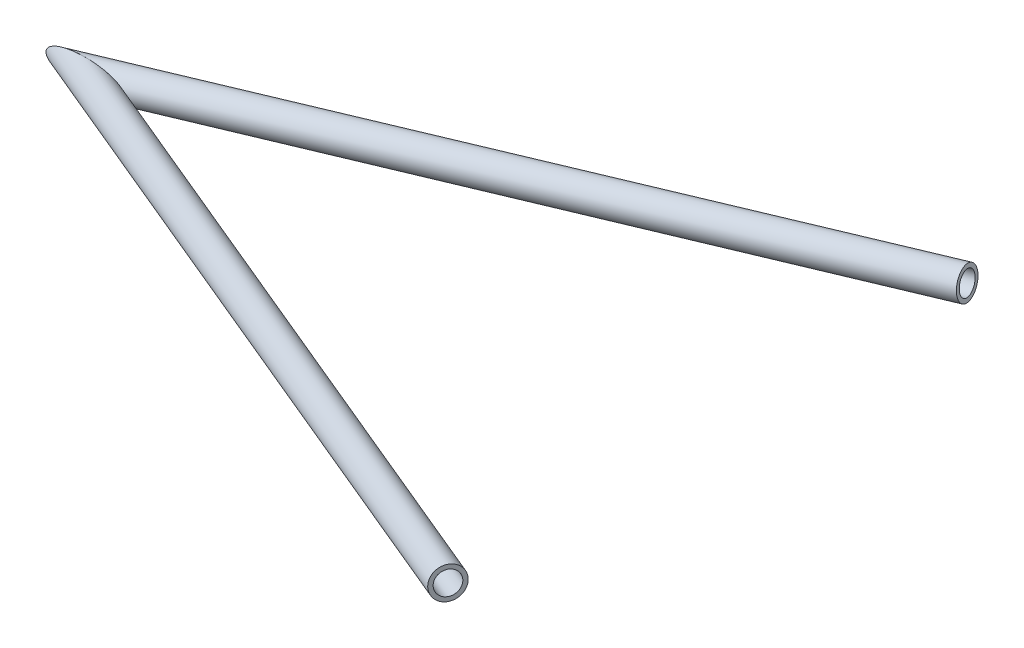
SolidWorks part; units mm, degrees
note: '?' marks a value the reader was unsure of.
material "AISI 4130 Steel, annealed at 865C"
ref_plane "Front Plane" through (0, 0, 0) normal (0, 0, 1) x (1, 0, 0)
ref_plane "Top Plane" through (0, 0, 0) normal (0, 1, 0) x (1, 0, 0)
ref_plane "Right Plane" through (0, 0, 0) normal (1, 0, 0) x (0, 0, -1)
sketch3d "reference sketch"
  line L2 (1.0874, 3.2881, 0) -> (435, 47.9009, -118.6)
  line L3 (435, 47.9009, 206.8) -> (1.0874, 3.2881, 0)
sketch3d "3DSketch2"
  line L0 (435, 47.9009, 206.8) -> (1.0874, 3.2881, 0) construction
  line L1 (1.0874, 3.2881, 0) -> (435, 47.9009, -118.6) construction
  line L2 (435, 47.9009, 206.8) -> (1.0874, 3.2881, 0)
  line L3 (1.0874, 3.2881, 0) -> (435, 47.9009, -118.6)
other "Pipe standard s40 PIPE 1 SCH 40(1)" corner treatment miter
ref_plane "Plane1" through (1.0874, 3.2881, 0) normal (0.9599, 0.0987, -0.2624) x (-0.2492, -0.1284, -0.9599)
sketch "Sketch1" plane through (1.0874, 3.2881, 0) normal (0.9599, 0.0987, -0.2624) x (-0.2492, -0.1284, -0.9599)
  circle A0 centre (0, 0) radius 6.985
  circle A1 centre (0, 0) radius 9.525
  point P3 (0, 0)
  dimension "D1" = 19.05
  dimension "D2" = 2.54
ref_axis "upper pivot axis" through (435, 47.9009, 206.8) along (0, 0, -1)?
ref_point "upper upright mounting point"
